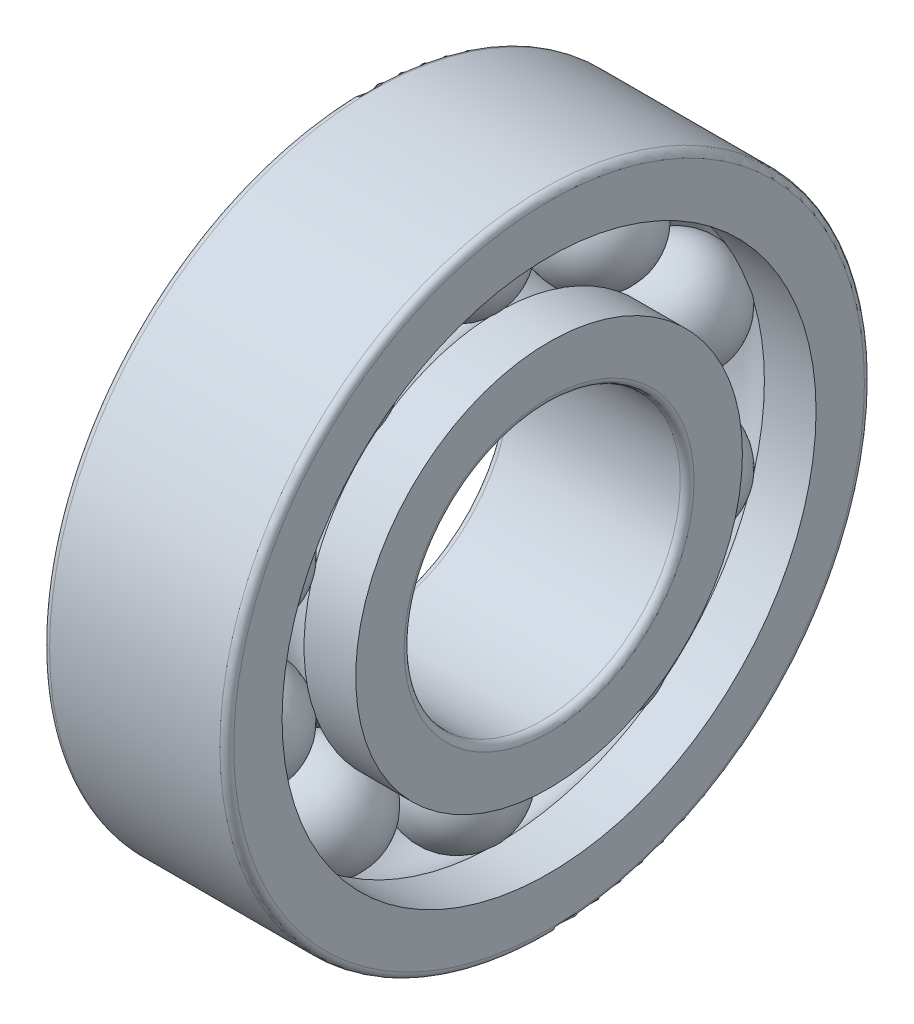
SolidWorks part; units mm, degrees
material "Alliage de zinc AC41A, brut"
ref_plane "Plane1" through (0, 0, 0) normal (0, 0, 1) x (1, 0, 0)
ref_plane "Plane2" through (0, 0, 0) normal (0, 1, 0) x (1, 0, 0)
ref_plane "Plane3" through (0, 0, 0) normal (1, 0, 0) x (0, 0, -1)
other "Configuration Table"
sketch "Clipboard" plane through (0, 0, 0) normal (0, 0, 1) x (1, 0, 0)
  line L0 (-10, 0) -> (10, 0) construction
  line L1 (0, 0) -> (22.021, -3.8829)
  line L2 (0, 0) -> (9.8481, 1.7365)
  line L3 (0, 0) -> (22.021, -3.8829)
  line L4 (0, 0) -> (-22.3573, -0.3902)
  dimension "BallCLRad" = 10
sketch "CagSpiSke" plane through (0, 0, 0) normal (0, 0, 1) x (1, 0, 0)
  line L0 (0.24, 9.6) -> (0.24, 10.4)
  line L1 (0.24, 10.4) -> (-0.24, 10.4)
  line L2 (-0.24, 10.4) -> (-0.24, 9.6)
  line L3 (-0.24, 9.6) -> (0.24, 9.6)
  line L4 (-20.6375, 0) -> (20.6375, 0) construction
  line L5 (0, 0) -> (0, 23.7692) construction
  dimension "OD" = 20.8
  dimension "ID" = 19.2
revolve "CageSpine" add sketch "CagSpiSke" angle 0.001 about L4 reverse direction yes
ref_axis "Axis1" through (-50, 0, 0) along (1, 0, 0)
sketch "CagBalSke" plane through (0, 0, 0) normal (0, 0, 1) x (1, 0, 0)
  line L0 (-2.64, 10) -> (2.64, 10)
  line L1 (-1.905, 10) -> (1.905, 10) construction
  line L2 (-10, 0) -> (10, 0) construction
  line L3 (0, 0) -> (0, 24) construction
  arc A0 (2.64, 10) -> (-2.64, 10) centre (0, 10) cw
  dimension "BallCLRad" = 10
revolve "CageBall" [suppressed] add sketch "CagBalSke" angle 360 about L1 reverse direction yes
pattern_circular "CageBalls" [suppressed] count 10 every 36 about axis through (-50, 0, 0) along (1, 0, 0)
sketch "CagTrmODSke" plane through (0, 0, 0) normal (0, 0, 1) x (1, 0, 0)
  line L0 (2.641, 10.4) -> (2.641, 12.641)
  line L1 (2.641, 12.641) -> (-2.641, 12.641)
  line L2 (-2.641, 12.641) -> (-2.641, 10.4)
  line L3 (-2.641, 10.4) -> (2.641, 10.4)
  line L4 (-20.6375, 0) -> (20.6375, 0) construction
  line L5 (0, 0) -> (0, 25) construction
  dimension "Width" = 5.282
  dimension "ID" = 20.8
  dimension "OD" = 25.282
revolve "CageTrimOD" [suppressed] cut sketch "CagTrmODSke" angle 360 about L4 reverse direction yes
sketch "CagTrmIDSke" plane through (0, 0, 0) normal (0, 0, 1) x (1, 0, 0)
  line L0 (2.641, 7.361) -> (2.641, 9.6)
  line L1 (2.641, 9.6) -> (-2.641, 9.6)
  line L2 (-2.641, 9.6) -> (-2.641, 7.361)
  line L3 (-2.641, 7.361) -> (2.641, 7.361)
  line L4 (-20.6375, 0) -> (20.6375, 0) construction
  line L5 (0, 0) -> (0, 25) construction
  dimension "Width" = 5.282
  dimension "ID" = 14.722
  dimension "OD" = 19.2
revolve "CageTrimID" [suppressed] cut sketch "CagTrmIDSke" angle 360 about L4 reverse direction yes
sketch "BalSimSke" plane through (0, 0, 0) normal (0, 0, 1) x (1, 0, 0)
  line L0 (-10, 0) -> (10, 0) construction
  line L1 (-10, 10) -> (10, 10) construction
  line L2 (0, 0) -> (0, 23) construction
  circle A0 centre (0, 10) radius 2.4
  dimension "BallCLRad" = 10
  dimension "Ball_diameter" = 4.8
revolve "BallsSimplified" [suppressed] add sketch "BalSimSke" angle 360 about L0
sketch "BalDetSke" plane through (0, 0, 0) normal (0, 0, 1) x (1, 0, 0)
  line L0 (-2.4, 10) -> (2.4, 10)
  line L1 (-1.905, 10) -> (1.905, 10) construction
  line L2 (0, 0) -> (0, 25) construction
  arc A0 (2.4, 10) -> (-2.4, 10) centre (0, 10) cw
  dimension "BallCLRad" = 10
  dimension "Ball_diameter" = 4.8
revolve "BallDetailed" add sketch "BalDetSke" angle 360 about L1 reverse direction yes
sketch "InnRacSke" plane through (0, 0, 0) normal (0, 0, 1) x (1, 0, 0)
  line L0 (-1.7552, 8.4) -> (-4, 8.4)
  line L1 (-4, 8.4) -> (-4, 6.3)
  line L2 (-3.7, 6) -> (3.7, 6)
  line L3 (4, 6.3) -> (4, 8.4)
  line L4 (4, 8.4) -> (1.7552, 8.4)
  line L5 (-20.6375, 0) -> (20.6375, 0) construction
  line L6 (0, 0) -> (0, 30) construction
  arc A0 (-4, 6.3) -> (-3.7, 6) centre (-3.7, 6.3) ccw
  arc A1 (3.7, 6) -> (4, 6.3) centre (3.7, 6.3) ccw
  arc A2 (1.7552, 8.4) -> (-1.7552, 8.4) centre (0, 10) cw
  dimension "BallCLRad" = 10
  dimension "Fillet_radius" = 0.3
  dimension "Ball_diameter" = 4.75
  dimension "ID" = 12
  dimension "OD" = 16.8
  dimension "Width" = 8
revolve "InnerRace" add sketch "InnRacSke" angle 360 about L5 reverse direction yes
sketch "OutRacSke" plane through (0, 0, 0) normal (0, 0, 1) x (1, 0, 0)
  line L0 (-1.7552, 11.6) -> (-4, 11.6)
  line L1 (-4, 11.6) -> (-4, 13.7)
  line L2 (-3.7, 14) -> (3.7, 14)
  line L3 (4, 13.7) -> (4, 11.6)
  line L4 (4, 11.6) -> (1.7552, 11.6)
  line L5 (-20.6375, 0) -> (20.6375, 0) construction
  line L6 (0, 0) -> (0, 30) construction
  arc A0 (-4, 13.7) -> (-3.7, 14) centre (-3.7, 13.7) cw
  arc A1 (3.7, 14) -> (4, 13.7) centre (3.7, 13.7) cw
  arc A2 (1.7552, 11.6) -> (-1.7552, 11.6) centre (0, 10) ccw
  dimension "BallCLRad" = 10
  dimension "Fillet_radius" = 0.3
  dimension "Ball_diameter" = 4.75
  dimension "Width" = 8
revolve "OuterRace" add sketch "OutRacSke" angle 360 about L5 reverse direction yes
pattern_circular "BallsDetailed" count 10 every 36 about axis through (-50, 0, 0) along (1, 0, 0) of "BallDetailed"
equation "\"BallCLRad@Clipboard\" = ( \"OD@OutRacSke\" + \"ID@InnRacSke\" ) / 4"
equation "\"BallCLRad@BalSimSke\" = \"BallCLRad@Clipboard\""
equation "\"BallCLRad@BalDetSke\" = \"BallCLRad@Clipboard\""
equation "\"BallCLRad@InnRacSke\" = \"BallCLRad@Clipboard\""
equation "\"BallCLRad@OutRacSke\" = \"BallCLRad@Clipboard\""
equation "\"Ball_diameter@InnRacSke\" = \"Ball_diameter@BalDetSke\" - 0.05"
equation "\"Ball_diameter@OutRacSke\" = \"Ball_diameter@BalDetSke\" - 0.05"
equation "\"Ball_diameter@BalSimSke\" = \"Ball_diameter@BalDetSke\""
equation "\"Width@OutRacSke\" = \"Width@InnRacSke\""
equation "\"Fillet_radius@OutRacSke\" = \"Fillet_radius@InnRacSke\""
equation "\"Max_count@Clipboard\" = int( 3.14159265 / atn(( \"Ball_diameter@BalDetSke\" / 2) / sqr( \"BallCLRad@Clipboard\"  *  \"BallCLRad@Clipboard\" - ( \"Ball_diameter@BalDetSke\" / 2) *  ( \"Ball_diameter@BalDetSke\" / 2))))"
equation "\"Max_count@Clipboard\" = ((sgn( \"Max_count@Clipboard\" - \"Count@Clipboard\" )-1)*( \"Max_count@Clipboard\" - \"Count@Clipboard\" ))/-2+ \"Count@Clipboard\""
equation "\"Count@BallsDetailed\" = int( \"Show_count@Clipboard\" ) "
equation "\"Count@BallsDetailed\" = ((sgn( \"Count@BallsDetailed\" - \"Max_count@Clipboard\" )-1)*( \"Count@BallsDetailed\" - \"Max_count@Clipboard\" ))/-2+ \"Max_count@Clipboard\""
equation "\"Count@BallsDetailed\" = ((sgn( \"Count@BallsDetailed\" - \"Min_count@Clipboard\" )+1)*( \"Count@BallsDetailed\" - \"Min_count@Clipboard\"))/2 +\"Min_count@Clipboard\""
equation "\"Angle@BallsDetailed\" = 360.0 / \"Max_count@Clipboard\""
equation "\"BallCLRad@CagBalSke\" = \"BallCLRad@Clipboard\""
equation "\"Count@CageBalls\" = \"Count@BallsDetailed\""
equation "\"Angle@CageBalls\" = \"Angle@BallsDetailed\""
equation "\"Angle@CageSpine\" =  \"Angle@CageBalls\" * ( \"Count@CageBalls\" -1 + int( \"Count@CageBalls\" / \"Max_count@Clipboard\" ) )  + 0.001 -  int( \"Count@CageBalls\" / \"Max_count@Clipboard\" ) * 0.001"
equation "\"Angle@CageSpine\" =  \"Angle@CageSpine\" * int( \"Min_count@Clipboard\" / 2) + int(1 / \"Min_count@Clipboard\")  * 0.001"
equation "\"CageWallOD@CagBalSke\" =  \"Ball_diameter@BalDetSke\" * 1.1"
equation "\"Thickness@CagSpiSke\" =  \"Ball_diameter@BalDetSke\" * 0.1"
equation "\"OD@CagTrmODSke\" = \"BallCLRad@Clipboard\" * 2 + \"CageWallOD@CagBalSke\" + 0.002"
equation "\"ID@CagTrmODSke\" = \"BallCLRad@Clipboard\" * 2 + \"Ball_diameter@BalDetSke\" / 6"
equation "\"OD@CagTrmIDSke\" = \"BallCLRad@Clipboard\" * 2 - \"Ball_diameter@BalDetSke\" / 6"
equation "\"ID@CagTrmIDSke\" = \"BallCLRad@Clipboard\" * 2 - \"CageWallOD@CagBalSke\" + 0.002"
equation "\"OD@CagSpiSke\" = \"ID@CagTrmODSke\""
equation "\"ID@CagSpiSke\" = \"OD@CagTrmIDSke\""
equation "\"Width@CagTrmODSke\" = \"CageWallOD@CagBalSke\" + 0.002"
equation "\"Width@CagTrmIDSke\" = \"CageWallOD@CagBalSke\" + 0.002"
